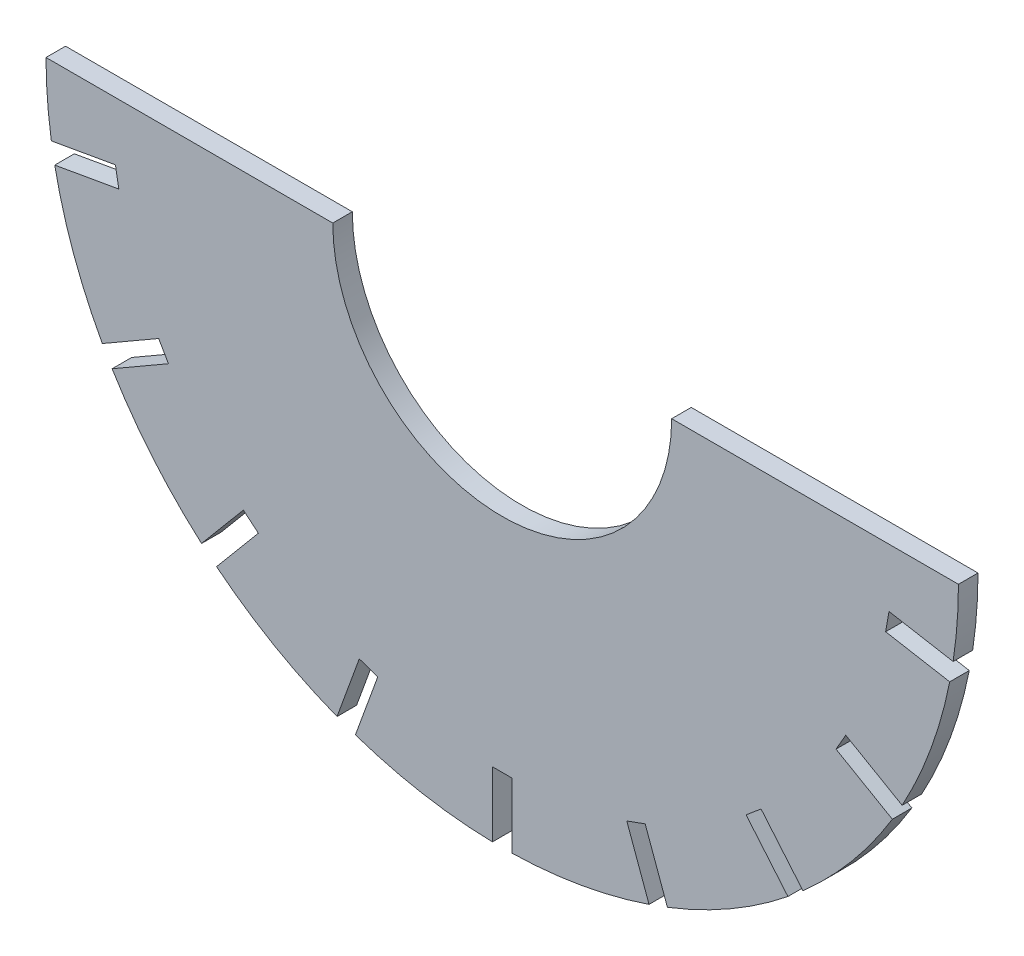
SolidWorks part; units mm, degrees
ref_plane "Front Plane" through (0, 0, 0) normal (0, 0, 1) x (1, 0, 0)
ref_plane "Top Plane" through (0, 0, 0) normal (0, 1, 0) x (1, 0, 0)
ref_plane "Right Plane" through (0, 0, 0) normal (1, 0, 0) x (0, 0, -1)
sketch "Sketch4" plane through (0, 0, 0) normal (0, 0, 1) x (1, 0, 0)
  line L1 (70, 0) -> (-70, 0)
  arc A0 (-70, 0) -> (70, 0) centre (0, 0) ccw
  dimension "D1" = 140
extrude "Boss-Extrude1" add sketch "Sketch4" along normal blind 3
sketch "Sketch5" plane through (0, 0, 0) normal (0, 0, 1) x (1, 0, 0)
  line L1 (-1.5, -60) -> (-1.5, -70)
  line L2 (-1.5, -60) -> (1.5, -60)
  line L4 (-1.5, -70) -> (1.5, -70)
  line L5 (1.5, -60) -> (1.5, -70)
extrude "Cut-Extrude2" cut sketch "Sketch5" along normal through all
ref_axis "Axis1" through (0, 0, 3) along (0, 0, -1)
pattern_circular "CirPattern1" count 5 every 20 about axis through (0, 0, 3) along (0, 0, -1) of "Cut-Extrude2" other way count 5
sketch "Sketch6" plane through (0, 0, 0) normal (0, 0, 1) x (1, 0, 0)
  circle A0 centre (0, 0) radius 26
  dimension "D1" = 52
extrude "Cut-Extrude3" cut sketch "Sketch6" along normal through all
